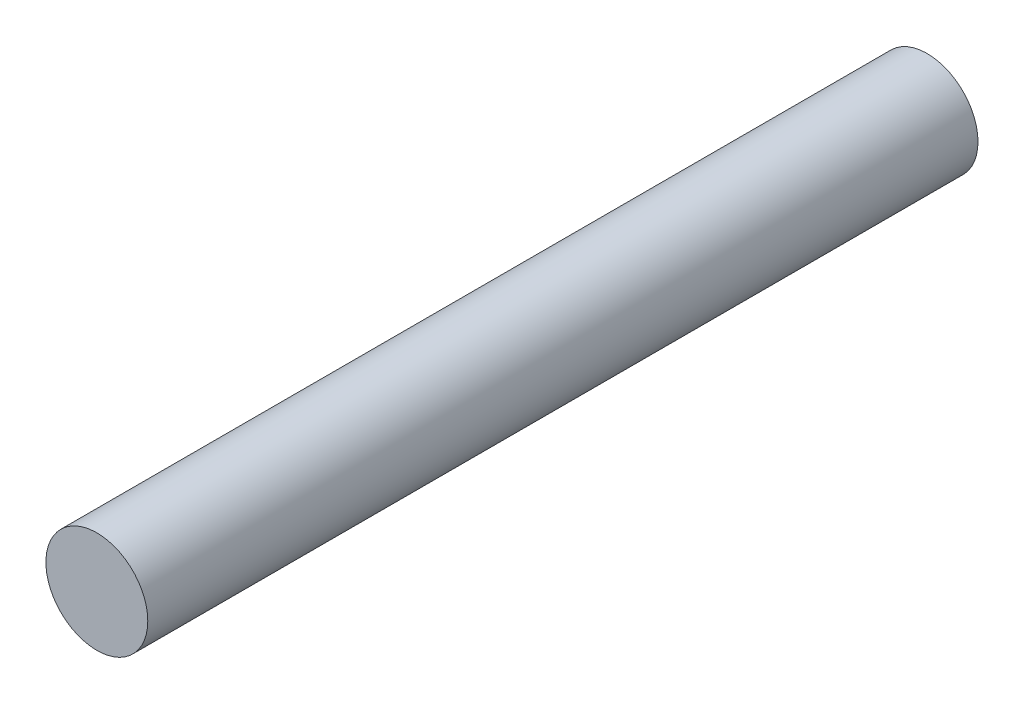
SolidWorks part; units mm, degrees
material "Hexcel AS4C (3000 Filaments)"
ref_plane "Front" through (0, 0, 0) normal (0, 0, 1) x (1, 0, 0)
ref_plane "Top" through (0, 0, 0) normal (0, 1, 0) x (1, 0, 0)
ref_plane "Right" through (0, 0, 0) normal (1, 0, 0) x (0, 0, -1)
sketch "Sketch1" plane through (0, 0, 0) normal (0, 0, 1) x (1, 0, 0)
  circle A0 centre (0, 0) radius 3.175
  dimension "D1" = 6.35
extrude "Boss-Extrude1" add sketch "Sketch1" along normal blind 51.7474
equation "\"truss_member_od\" = .25in"
equation "\"truss_member_L1\" = 2.125in"
equation "\"connector_hole_depth\" = .375in"
equation "\"truss_member_L2\" = 3in"
equation "\"D1@Boss-Extrude1\"=\"truss_member_L1\""
equation "\"D1@Sketch1\"=\"truss_member_od\""
